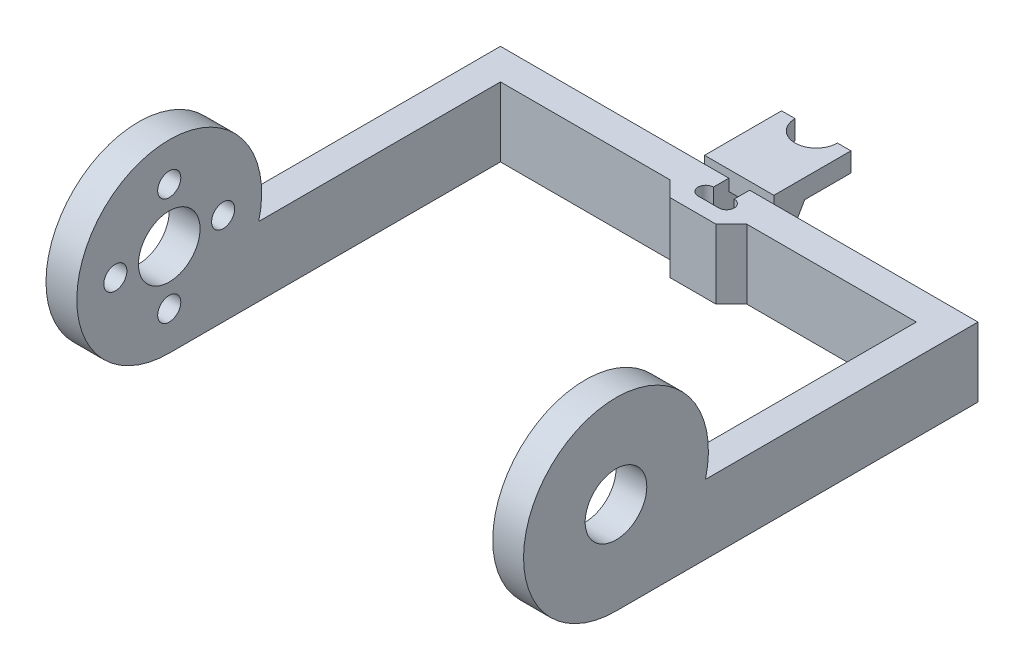
SolidWorks part; units mm, degrees
ref_plane "前视基准面" through (0, 0, 0) normal (0, 0, 1) x (1, 0, 0)
ref_plane "上视基准面" through (0, 0, 0) normal (0, 1, 0) x (1, 0, 0)
ref_plane "右视基准面" through (0, 0, 0) normal (1, 0, 0) x (0, 0, -1)
sketch "Sketch1" plane through (0, 0, 0) normal (1, 0, 0) x (0, 0, -1)
  line L2 (47, -12) -> (0, -12)
  line L4 (47, -3) -> (47, -12)
  line L5 (47, -3) -> (11.619, -3)
  arc A0 (11.619, -3) -> (0, -12) centre (0, 0) ccw
  point P19 (47, -7.5)
  dimension "D1" = 47
  dimension "D2" = 24
  dimension "D6" = 9
extrude "Boss-Extrude1" add sketch "Sketch1" against normal blind 62
sketch "Sketch2" plane through (0, 0, 0) normal (0, 1, 0) x (1, 0, 0)
  line L0 (-58, -12) -> (-58, 43)
  line L1 (-62, 47) -> (0, 47) construction
  line L2 (-62, 47) -> (-62, -12) construction
  line L3 (-62, -12) -> (0, -12) construction
  line L4 (0, 47) -> (0, -12) construction
  line L5 (-58, 43) -> (-36, 43)
  line L6 (-4, 43) -> (-4, -12)
  line L7 (-4, -12) -> (-58, -12)
  line L9 (-26, 43) -> (-4, 43)
  line L10 (-36, 41) -> (-26, 41)
  line L11 (-36, 41) -> (-36, 43)
  line L13 (-26, 41) -> (-26, 43)
  line L14 (-36, 41) -> (-26, 43) construction
  line L15 (-36, 43) -> (-26, 41) construction
  point P6 (0, 0)
  point P11 (0, 0)
  point P12 (-31, 42)
  dimension "D1" = 4
  dimension "D2" = 4
  dimension "D3" = 4
  dimension "D4" = 2
  dimension "D5" = 10
extrude "Cut-Extrude1" cut sketch "Sketch2" against normal blind 12 and the other way blind 12
sketch "Sketch3" plane through (0, -3, 0) normal (0, 1, 0) x (1, 0, 0)
  line L0 (-35.5, 57) -> (-35.5, 47)
  line L1 (-35.5, 47) -> (-26.5, 47)
  line L2 (-35.5, 57) -> (-26.5, 57) construction
  line L3 (-26.5, 47) -> (-26.5, 57)
  line L4 (-35.5, 57) -> (-33.75, 57)
  line L6 (-62, 47) -> (0, 47) construction
  line L8 (-28.25, 57) -> (-26.5, 57)
  arc A0 (-33.75, 57) -> (-28.25, 57) centre (-31, 57) ccw
  point P3 (-31, 47)
  dimension "D3" = 2.75
  dimension "D1" = 10
  dimension "D2" = 9
extrude "Boss-Extrude2" add sketch "Sketch3" along normal blind 1 and the other way blind 1.5
sketch "Sketch5" plane through (0, -3, 0) normal (0, 1, 0) x (1, 0, 0)
  line L2 (-31, 43) -> (-31, 47) construction
  line L3 (-62, 47) -> (-35.5, 47) construction
  line L4 (-32.35, 44) -> (-29.65, 44) construction
  line L5 (-32.35, 43) -> (-29.65, 43)
  line L6 (-32.35, 45) -> (-32.35, 47)
  line L7 (-32.35, 47) -> (-29.65, 47)
  line L8 (-29.65, 47) -> (-29.65, 45)
  line L10 (-35.5, 47) -> (-26.5, 47) construction
  arc A0 (-32.35, 45) -> (-32.35, 43) centre (-32.35, 44) ccw
  arc A1 (-29.65, 45) -> (-29.65, 43) centre (-29.65, 44) cw
  point P0 (-31, 44)
  dimension "D1" = 2.7
  dimension "D2" = 1
  dimension "D3" = 2
extrude "Cut-Extrude3" cut sketch "Sketch5" against normal blind 10
chamfer "Chamfer2" distance 2 angle 45 1 edges at (-26, -7.5, -41)
chamfer "Chamfer3" distance 2 angle 45 1 edges at (-36, -7.5, -41)
chamfer "Chamfer4" distance 4 angle 60 2 edges at (-33.925, -4.5, -47) (-28.075, -4.5, -47) first distance on face at (-31, -4.5, -51.6562)
sketch "Sketch7" plane through (0, 0, 0) normal (1, 0, 0) x (0, 0, -1)
  circle A0 centre (0, 0) radius 4
extrude "Cut-Extrude4" cut sketch "Sketch7" against normal blind 70
sketch "Sketch8" plane through (-62, 0, 0) normal (-1, 0, 0) x (0, 0, 1)
  line L0 (0, 0) -> (0, 7) construction
  circle A0 centre (0, 7) radius 1.5
  circle A1 centre (7, 0) radius 1.5
  circle A2 centre (0, -7) radius 1.5
  circle A3 centre (-7, 0) radius 1.5
  point P13 (0, 0)
extrude "Cut-Extrude5" cut sketch "Sketch8" against normal up to next
